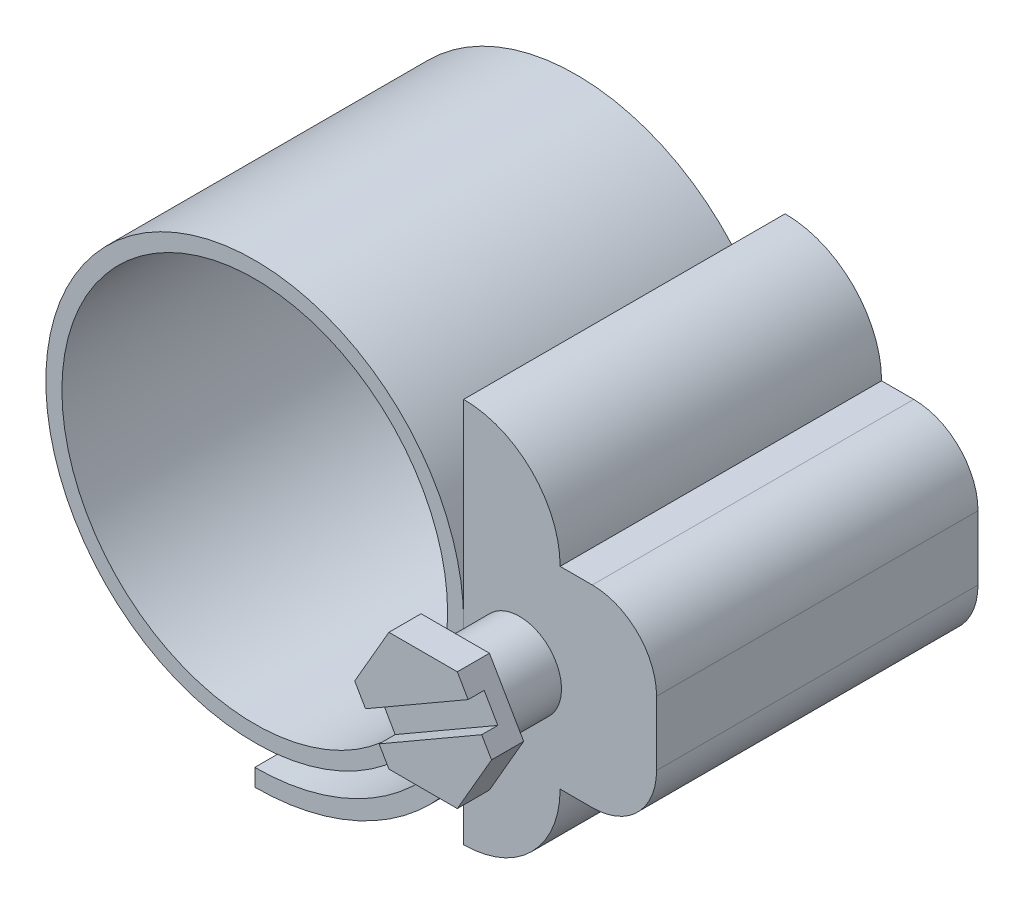
SolidWorks part; units mm, degrees
material "Latão"
ref_plane "Plano frontal" through (0, 0, 0) normal (0, 0, 1) x (1, 0, 0)
ref_plane "Plano superior" through (0, 0, 0) normal (0, 1, 0) x (1, 0, 0)
ref_plane "Plano direito" through (0, 0, 0) normal (1, 0, 0) x (0, 0, -1)
sketch "Esboço1" plane through (0, 0, 0) normal (0, 0, 1) x (1, 0, 0)
  circle A0 centre (0, 0) radius 6.5
  circle A1 centre (0, 0) radius 6
  dimension "D1" = 12
  dimension "D2" = 13
extrude "Ressalto-extrusão1" add sketch "Esboço1" along normal blind 10
sketch "Esboço2" plane through (0, 0, 10) normal (0, 0, 1) x (1, 0, 0)
  line L0 (6.5, 0) -> (6.5, 6)
  line L1 (6.5, 6) -> (9.5, 6)
  line L2 (9.5, 6) -> (9.5, -6)
  line L3 (9.5, -6) -> (6.5, -6)
  line L4 (6.5, -6) -> (6.5, 0)
  circle A0 centre (0, 0) radius 6.5 construction
  dimension "D1" = 3
  dimension "D2" = 6
  dimension "D3" = 12
extrude "Ressalto-extrusão2" add sketch "Esboço2" against normal blind 10 separate body
sketch "Esboço3" plane through (9.5, 0, 0) normal (1, 0, 0) x (0, 0, -1)
  line L0 (0, 0) -> (0, 3)
  line L1 (0, -6) -> (0, 6) construction
  line L2 (0, 3) -> (-10, 3)
  line L3 (-10, -6) -> (-10, 6) construction
  line L4 (-10, 3) -> (-10, -3)
  line L5 (-10, -3) -> (0, -3)
  line L6 (0, -3) -> (0, 0)
  dimension "D1" = 3
  dimension "D2" = 3
extrude "Ressalto-extrusão3" add sketch "Esboço3" along normal blind 3
fillet "Filete1" radius 2 2 edges at (12.5, -3, 5) (12.5, 3, 5)
fillet "Filete2" radius 3 2 edges at (9.5, -6, 5) (9.5, 6, 5)
sketch "Esboço4" plane through (0, 0, 10) normal (0, 0, 1) x (1, 0, 0)
  circle A0 centre (8.2375, -0.2818) radius 1.3041
extrude "Ressalto-extrusão4" add sketch "Esboço4" along normal blind 2
sketch "Esboço5" plane through (0, 0, 12) normal (0, 0, 1) x (1, 0, 0)
  line L1 (10.3656, -0.2818) -> (9.3016, 1.5611)
  line L2 (9.3016, 1.5611) -> (7.1735, 1.5611)
  line L3 (7.1735, 1.5611) -> (6.1095, -0.2818)
  line L4 (6.1095, -0.2818) -> (7.1735, -2.1247)
  line L5 (7.1735, -2.1247) -> (9.3016, -2.1247)
  line L6 (9.3016, -2.1247) -> (10.3656, -0.2818)
  circle A0 centre (8.2375, -0.2818) radius 1.8429 construction
extrude "Ressalto-extrusão5" add sketch "Esboço5" along normal blind 1
sketch "Esboço6" plane through (0, 0, 13) normal (0, 0, 1) x (1, 0, 0)
  line L0 (9.8336, 0.6396) -> (9.6372, 0.9797)
  line L1 (10.3656, -0.2818) -> (9.3016, 1.5611) construction
  line L2 (9.6372, 0.9797) -> (6.4452, -0.8632)
  line L3 (6.1095, -0.2818) -> (7.1735, -2.1247) construction
  line L4 (6.4452, -0.8632) -> (6.869, -1.5972)
  line L5 (6.869, -1.5972) -> (10.061, 0.2457)
  line L6 (10.061, 0.2457) -> (9.6372, 0.9797)
  line M2 (10.3656, -0.2818) -> (9.3016, 1.5611)
  line M5 (6.1095, -0.2818) -> (7.1735, -2.1247)
extrude "Corte-extrusão1" cut sketch "Esboço6" against normal blind 0.5 contours L5 L2 M5 M2 region at (8.2531, -0.3088, 13)
sketch "Esboço7" plane through (0, 0, 10) normal (0, 0, 1) x (1, 0, 0)
  line L0 (6.5, -4.1279) -> (6.5, -3.0138)
  line L1 (6.5, 6) -> (6.5, -6) construction
  line L2 (0, -7.7) -> (0, -7.1647)
  circle A0 centre (0, 0) radius 7.1647
  circle A1 centre (0, 0) radius 7.7
extrude "Ressalto-extrusão6" add sketch "Esboço7" against normal blind 10 contours L2 A1 L0 A0 region at (3.6698, -6.6779, 10)
